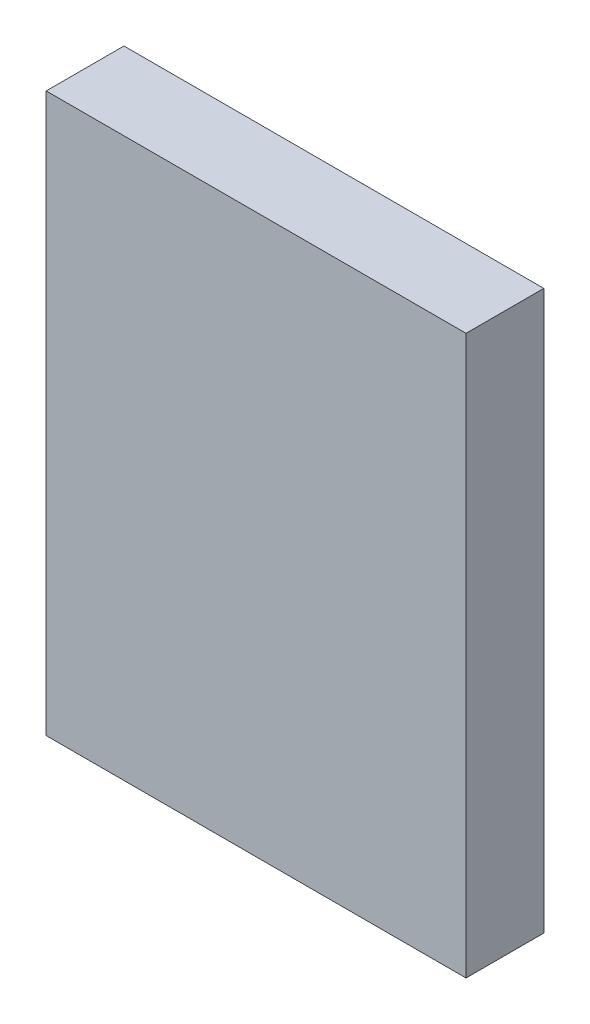
SolidWorks part; units mm, degrees
ref_plane "前视基准面" through (0, 0, 0) normal (0, 0, 1) x (1, 0, 0)
ref_plane "上视基准面" through (0, 0, 0) normal (0, 1, 0) x (1, 0, 0)
ref_plane "右视基准面" through (0, 0, 0) normal (1, 0, 0) x (0, 0, -1)
other "Configuration Table"
sketch "Model" plane through (0, 0, 0) normal (0, 0, 1) x (1, 0, 0)
  line L1 (102.1602, 94.3849) -> (102.1602, 82.3849)
  line L2 (102.1602, 35.8849) -> (102.1602, 29.862)
  line L3 (179.3095, 94.3849) -> (179.3095, 82.3849)
  line L4 (179.3095, 35.8849) -> (179.3095, 29.862)
  line L5 (179.3095, 35.8849) -> (179.3095, 29.862)
  line L6 (139.622, 29.862) -> (102.1602, 29.862)
  line L7 (92.1602, 156.0615) -> (189.3095, 156.0615)
  line L8 (92.1602, 156.0615) -> (92.1602, 26.862)
  line L9 (92.1602, 26.862) -> (189.3095, 26.862)
  line L10 (189.3095, 156.0615) -> (189.3095, 26.862)
  line L11 (102.1856, 29.862) -> (179.3095, 29.862) construction
  line L12 (102.1602, 29.862) -> (179.3095, 29.862) construction
  line L13 (102.1602, 29.862) -> (179.3095, 29.862)
  line L14 (102.1602, 118.9846) -> (102.1602, 126.0615)
  line L16 (179.3095, 29.862) -> (179.3095, 151.036) construction
  line L17 (102.1602, 126.0615) -> (179.3095, 126.0615) construction
  line L18 (179.3095, 126.0615) -> (179.3095, 118.9846)
  line L19 (102.1602, 126.0615) -> (102.1856, 151.036)
  line L20 (102.1856, 151.036) -> (179.3095, 151.036)
  line L21 (179.3095, 151.036) -> (179.3095, 126.0615)
  line L171 (102.1602, 94.3849) -> (102.1602, 118.9846)
  line L172 (102.1602, 35.8849) -> (102.1602, 82.3849)
  line L173 (179.3095, 35.8849) -> (179.3095, 82.3849)
  line L174 (179.3095, 35.8849) -> (179.3095, 82.3849)
  line L175 (179.3095, 118.9846) -> (179.3095, 94.3849)
extrude "凸台-拉伸1" add sketch "Model" along normal blind 15 contours L175 L3 L173 L4 L2 L172 L1 L171 region at (140.7349, 154.445, 0)
sketch "草图5" plane through (0, 0, 15) normal (0, 0, 1) x (1, 0, 0)
  line L5 (92.1602, 156.0615) -> (189.3095, 156.0615)
  line L6 (92.1602, 156.0615) -> (92.1602, 26.862)
  line L7 (92.1602, 26.862) -> (189.3095, 26.862)
  line L8 (189.3095, 156.0615) -> (189.3095, 26.862)
extrude "凸台-拉伸2" add sketch "草图5" along normal blind 3
sketch "草图4" plane through (0, 0, 0) normal (0, 0, 1) x (1, 0, 0)
  line L164 (102.1602, 42.3849) -> (102.1602, 17.3849)
  line L186 (179.3095, 100.8849) -> (179.3095, 75.8849)
  line L187 (179.3095, 75.8849) -> (187.3095, 75.8849)
  line L188 (102.1602, 100.8849) -> (102.1602, 75.8849)
  line L189 (102.1602, 100.8849) -> (94.1602, 100.8849)
  line L190 (102.1602, 75.8849) -> (94.1602, 75.8849)
  line L191 (94.1602, 100.8849) -> (94.1602, 75.8849)
  line L192 (187.3095, 100.8849) -> (187.3095, 75.8849)
  line L193 (179.3095, 100.8849) -> (187.3095, 100.8849)
  line L194 (179.3095, 42.3849) -> (179.3095, 17.3849)
  line L195 (179.3095, 42.3849) -> (187.3095, 42.3849)
  line L196 (187.3095, 42.3849) -> (187.3095, 17.3849)
  line L198 (102.1602, 42.3849) -> (94.1602, 42.3849)
  line L199 (102.1602, 17.3849) -> (94.1602, 17.3849)
  line L200 (94.1602, 42.3849) -> (94.1602, 17.3849)
  line L201 (179.3095, 17.3849) -> (187.3095, 17.3849)
extrude "切除-拉伸1" cut sketch "草图4" along normal blind 2
